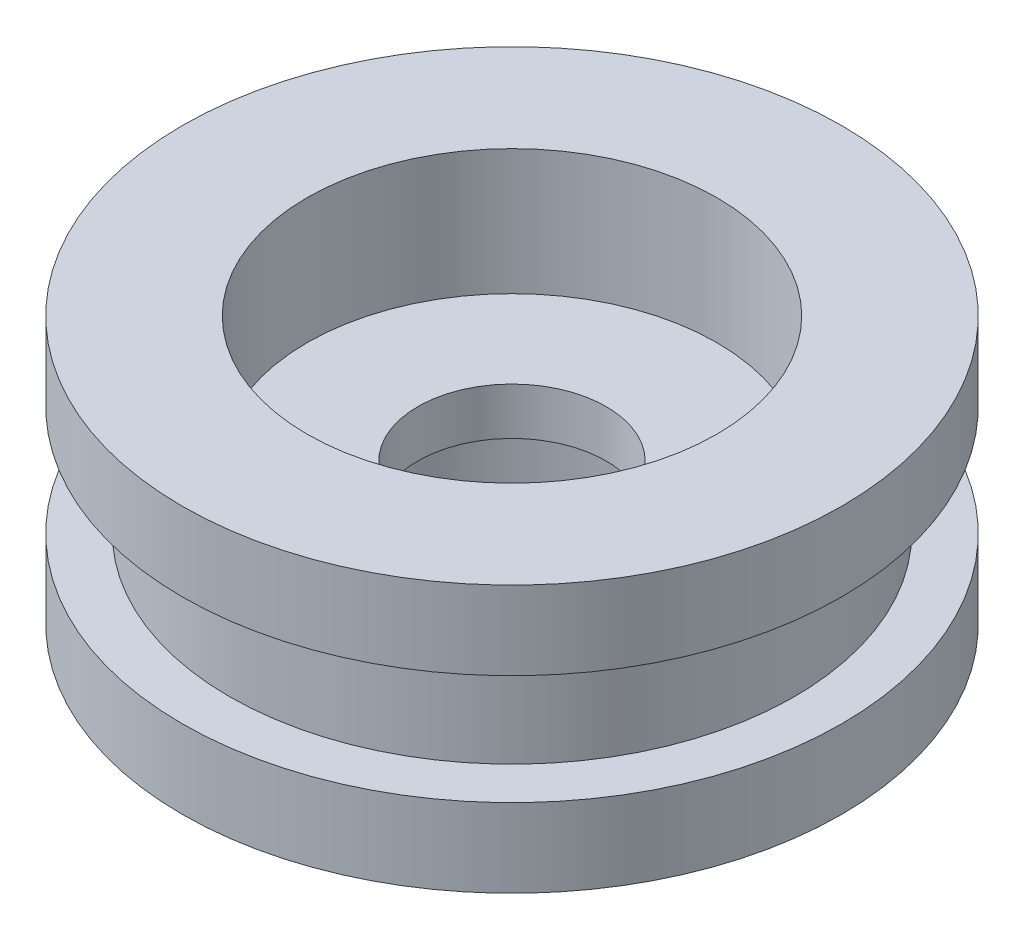
SolidWorks part; units mm, degrees
ref_plane "Front Plane" through (0, 0, 0) normal (0, 0, 1) x (1, 0, 0)
ref_plane "Top Plane" through (0, 0, 0) normal (0, 1, 0) x (1, 0, 0)
ref_plane "Right Plane" through (0, 0, 0) normal (1, 0, 0) x (0, 0, -1)
sketch "Sketch2" plane through (0, 0, 0) normal (0, 0, 1) x (1, 0, 0)
  line L0 (0, 17.2621) -> (0, -17.2621) construction
  line L1 (6, 1.5) -> (13.05, 1.5)
  line L2 (13.05, 1.5) -> (13.05, 9.5)
  line L3 (13.05, 9.5) -> (21, 9.5)
  line L4 (21, 9.5) -> (21, 4.5)
  line L5 (21, 4.5) -> (18, 4.5)
  line L6 (18, 4.5) -> (18, -2.5)
  line L7 (18, -2.5) -> (21, -2.5)
  line L8 (21, -2.5) -> (21, -7.5)
  line L9 (21, -7.5) -> (18, -7.5)
  line L10 (18, -7.5) -> (18, -9.5)
  line L11 (18, -9.5) -> (13.05, -9.5)
  line L12 (13.05, -9.5) -> (13.05, -1.5)
  line L13 (13.05, -1.5) -> (6, -1.5)
  line L14 (6, -1.5) -> (6, 1.5)
  point P3 (6, 0)
  point P4 (0, 0)
  dimension "D1" = 7
  dimension "D2" = 26.1
  dimension "D3" = 8
  dimension "D4" = 12
  dimension "D5" = 5
  dimension "D6" = 3
  dimension "D7" = 3
  dimension "D8" = 5
  dimension "D9" = 36
revolve "Revolve1" add sketch "Sketch2" angle 360 about L0
